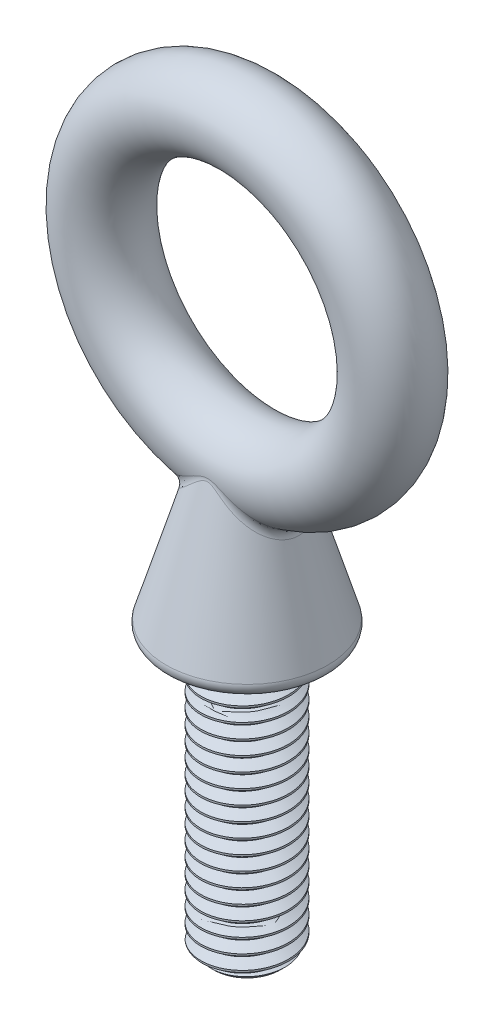
SolidWorks part; units mm, degrees
note: '?' marks a value the reader was unsure of.
ref_plane "Front Plane" through (0, 0, 0) normal (0, 0, 1) x (1, 0, 0)
ref_plane "Top Plane" through (0, 0, 0) normal (0, 1, 0) x (1, 0, 0)
ref_plane "Right Plane" through (0, 0, 0) normal (1, 0, 0) x (0, 0, -1)
sketch "Sketch1" plane through (0, 0, 0) normal (0, 0, 1) x (1, 0, 0)
  line L0 (0, -23.4156) -> (0, -72.6281) construction
  line L1 (-5.5562, -72.6281) -> (5.5563, -72.6281) construction
  line L2 (5.7527, -72.5147) -> (5.7527, -74.329) construction
  line L3 (0, -23.4156) -> (0, -13.4937) construction
  line L4 (-10.3187, -37.7031) -> (10.3188, -37.7031) construction
  line L5 (5.7527, -74.329) -> (4.1814, -73.4219) construction
  line L6 (4.1814, -73.4219) -> (5.7527, -72.5147) construction
  line L7 (4.1814, -73.4219) -> (4.3778, -73.4219) construction
  line L8 (5.7527, -73.4219) -> (5.5563, -73.4219) construction
  line L9 (4.3778, -73.5353) -> (4.3778, -73.3085) construction
  line L10 (5.5563, -74.2156) -> (5.5563, -72.6281) construction
  line L11 (5.6545, -74.2723) -> (5.6545, -72.5714) construction
  circle A0 centre (0, 0) radius 23.4156 construction
  circle A1 centre (0, 18.4547) radius 4.9609 construction
  circle A2 centre (0, 0) radius 13.4938 construction
  point P7 (0, -23.4156)
  point P9 (0, -37.7031)
  point P10 (0, 23.4156)
  point P11 (0, 13.4937)
  point P14 (0, -72.6281)
  point P17 (0, 0)
  point P19 (0, -18.4547)
  point P21 (0, -37.7031)
  point P32 (4.3778, -73.4219)
  point P35 (5.5563, -73.4219)
  point P38 (5.6545, -73.4219)
  dimension "Pitch" = 1.8143
  dimension "D1" = 0.2268
sketch "Sketch2" plane through (0, 0, 0) normal (0, 1, 0) x (1, 0, 0)
  circle A0 centre (0, 0) radius 5.5563
extrude "Boss-Extrude1" add sketch "Sketch2" against normal up to vertex (72.6281 mm away) from vertex at -37.7031 starting at point (0, -37.7031, 0)
sketch "Sketch3" plane through (0, -72.6281, 0) normal (0, -1, 0) x (1, 0, 0)
  circle A1 centre (0, 0) radius 5.5563
  circle A2 centre (0, 0) radius 5.5563
  point P0 (5.5563, 0)
  point P1 (0, -5.5563)
  dimension "D1" = 0
sketch "Sketch4" plane through (0, 0, 0) normal (0, 0, 1) x (1, 0, 0)
  line L0 (4.3778, -73.3085) -> (4.3778, -73.5353)
  line L1 (4.3778, -73.5353) -> (5.6545, -74.2723)
  line L2 (5.6545, -74.2723) -> (5.6545, -72.5714)
  line L3 (5.6545, -72.5714) -> (4.3778, -73.3085)
sketch "Sketch5" plane through (0, -72.6281, 0) normal (0, -1, 0) x (1, 0, 0)
  circle A0 centre (0, 0) radius 4.1814
extrude "Cut-Extrude1" cut sketch "Sketch5" against normal through all draft 45 flip side to cut
sketch "Sketch6" plane through (0, 0, 0) normal (1, 0, 0) x (0, 0, -1)
  circle A0 centre (0, 18.4547) radius 4.9609
ref_axis "Axis1" through (0, 0, -7.6398) along (0, 0, 1)
revolve "Revolve1" add sketch "Sketch6" angle 360 about axis through (0, 0, -7.6398) along (0, 0, 1)
sketch "Sketch8" plane through (0, 0, 0) normal (0, 0, 1) x (1, 0, 0)
  line L0 (0, -37.7031) -> (0, -18.4547)
  line L1 (0, -18.4547) -> (-4.9609, -18.4547)
  line L2 (-9.0785, -37.7031) -> (-10.3187, -37.7031) construction
  line L3 (-10.3187, -37.7031) -> (-10.3187, -36.4629) construction
  line L4 (0, -37.7031) -> (10.3187, -37.7031) construction
  line L5 (-10.3187, -37.7031) -> (10.3188, -37.7031) construction
  line L6 (-10.2663, -36.1059) -> (-4.9609, -18.4547)
  line L7 (-10.3187, -37.7031) -> (0, -37.7031) construction
  line L9 (-9.0785, -37.7031) -> (0, -37.7031)
  arc A0 (-10.2663, -36.1059) -> (-9.0785, -37.7031) centre (-9.0785, -36.4629) ccw
  circle A1 centre (0, -18.4547) radius 4.9609 construction
  dimension "D1" = 1.2402
revolve "Revolve2" add sketch "Sketch8" angle 360 about L0
fillet "Fillet1" radius 1.2402 1 edges at (4.8259, -21.5522, 3.3801)
sketch "SketchX" plane through (0, 0, 0) normal (1, 0, 0) x (0, 0, -1)
  line L0 (5.5562, -72.6281) -> (5.5562, -68.0924) construction
  line L1 (0, -72.6281) -> (5.5562, -72.6281) construction
  dimension "D1" = 4.5357
  dimension "D2" = 5.5562
ref_axis "Center Axis 1" through (0, 21.5506, 0) along (0, -1, 0)?
ref_axis "Center Axis 2" through (0, 0, -7.6398) along (0, 0, 1)?
curve "Helix/Spiral1" pitch 1.8143 height 36.7393 turns 20.25 parameters "Pitch"=1.8143
ref_plane "Plane1" through (0, -37.7031, 0) normal (0, -1, 0) x (1, 0, 0)
split "Split1" trim tools "Plane1" bodies to split 109 resulting bodies 110 111
sweep "Cut-Sweep1" cut profiles "Sketch4" path "Helix/Spiral1" align with end faces yes
sketch "Sketch9" plane through (0, -37.7031, 0) normal (0, -1, 0) x (1, 0, 0)
  line L0 (-10.3187, 0) -> (10.3188, 0) construction
  circle A0 centre (0, 0) radius 5.5562
extrude "Boss-Extrude2" add sketch "Sketch9" along normal blind 2.54 draft 45
equation "\"D3@Helix/Spiral1\" = \"Pitch@Helix/Spiral1\" + \"Thread Lg.@Sketch1\""
equation "\"D1@Sketch8\" = \"A@Sketch1\" / 8"
equation "\"D1@Fillet1\" = \"A@Sketch1\" / 8"
equation "\"D1@SketchX\"= \"Pitch@Helix/Spiral1\"*2.5"
equation "\"D1@Sketch1\"=\"Pitch@Sketch1\"/8"
equation "\"Pitch@Helix/Spiral1\"=\"Pitch@Sketch1\""
equation "\"D2@SketchX\" = \"Thread OD@Sketch1\" / 2"
